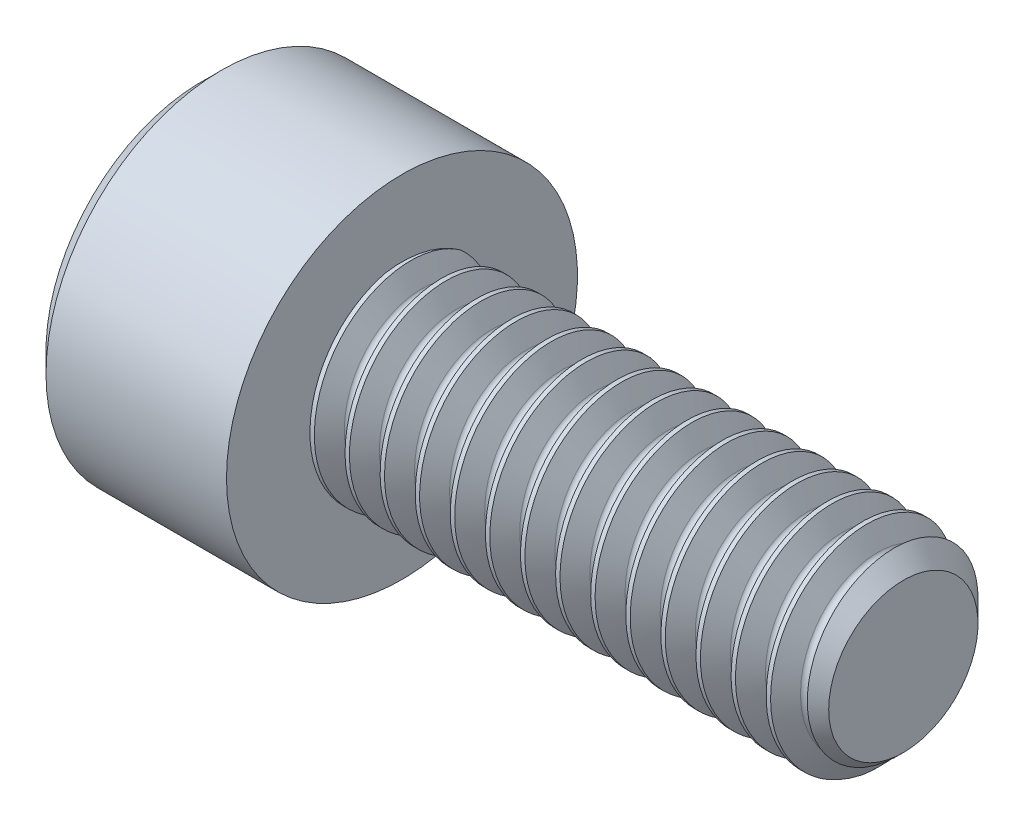
SolidWorks part; units mm, degrees
material "AISI Type 316L stainless steel"
ref_plane "Front Plane" through (0, 0, 0) normal (0, 0, 1) x (1, 0, 0)
ref_plane "Top Plane" through (0, 0, 0) normal (0, 1, 0) x (1, 0, 0)
ref_plane "Right Plane" through (0, 0, 0) normal (1, 0, 0) x (0, 0, -1)
sketch "Sketch1" plane through (0, 0, 0) normal (0, 0, 1) x (1, 0, 0)
  line L0 (-88.7055, 0) -> (96.9812, 0) construction
  line L1 (0, 0) -> (0, 3.5)
  line L2 (0, 3.5) -> (4, 3.5)
  line L4 (14, 0) -> (14, 1.989)
  line L5 (14, 1.989) -> (4, 1.989)
  line L6 (4, 1.989) -> (4, 3.5)
  line L7 (0, 0) -> (14, 0)
revolve "Revolve1" add sketch "Sketch1" angle 360 about L0
chamfer "Chamfer1" distance 0.5 angle 45 1 edges at (14, 0, 1.989)
chamfer "Chamfer2" distance 0.4 angle 45 1 edges at (0, 0, 3.5)
sketch "Sketch3" plane through (0, 0, 0) normal (1, 0, 0) x (0, 0, -1)
  line L1 (-1.7321, 0) -> (-0.866, -1.5)
  line L2 (-0.866, -1.5) -> (0.866, -1.5)
  line L3 (0.866, -1.5) -> (1.7321, 0)
  line L4 (1.7321, 0) -> (0.866, 1.5)
  line L5 (0.866, 1.5) -> (-0.866, 1.5)
  line L6 (-0.866, 1.5) -> (-1.7321, 0)
  circle A0 centre (0, 0) radius 1.5 construction
extrude "Cut-Extrude1" cut sketch "Sketch3" along normal blind 2
chamfer "Chamfer3" distance 0.3 angle 45 6 edges at (0, 1.5, 0) (0, 0.75, 1.299) (0, -0.75, 1.299) (0, -1.5, 0) (0, -0.75, -1.299) (0, 0.75, -1.299)
sketch "Sketch5" plane through (14, 0, 0) normal (1, 0, 0) x (0, 0, -1)
  circle A0 centre (0, 0) radius 1.989
curve "Helix/Spiral1" pitch 0.7 height 10 radius 1.989 centre (14, 0, 0) axis (-1, 0, 0) start towards (0, 0, -1)
sketch "Sketch8" plane through (0, 0, 0) normal (0, 1, 0) x (1, 0, 0)
  line L0 (14, 1.989) -> (14, 1.4588) construction
  line L1 (14.0875, 1.6102) -> (14.4592, 2.2541)
  line L2 (14.4592, 2.2541) -> (13.5408, 2.2541)
  line L3 (13.5408, 2.2541) -> (13.9125, 1.6102)
  line L4 (14, -1.489) -> (14, 1.489) construction
  circle A0 centre (14, 1.989) radius 0.2651 construction
  arc A1 (14.0875, 1.6102) -> (13.9125, 1.6102) centre (14, 1.6607) cw
  dimension "D2" = 0.101
  dimension "D1" = 0.5302
sweep "Cut-Sweep1" cut profiles "Sketch8" path "Helix/Spiral1" align with end faces yes
